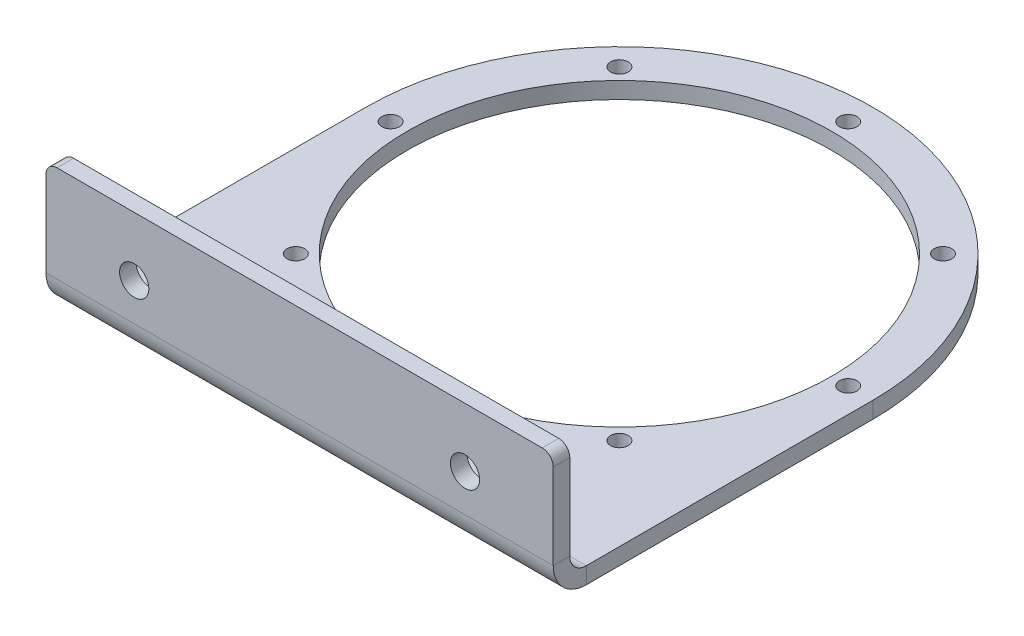
SolidWorks part; units mm, degrees
note: The reader was unsure of these and kept them because the rebuilt part matched: flange length of "Edge-Flange1".
material "3.3549 (EN-AW 5182)"
ref_plane "Front Plane" through (0, 0, 0) normal (0, 0, 1) x (1, 0, 0)
ref_plane "Top Plane" through (0, 0, 0) normal (0, 1, 0) x (1, 0, 0)
ref_plane "Right Plane" through (0, 0, 0) normal (1, 0, 0) x (0, 0, -1)
sketch "Sketch1" plane through (0, 0, 0) normal (0, 1, 0) x (1, 0, 0)
  line L0 (0, -44.7868) -> (0, 44.7868) construction
  line L1 (-46, 0) -> (-46, -55)
  line L2 (-46, -55) -> (46, -55)
  line L3 (46, -55) -> (46, 0)
  line L4 (-44.2539, 0) -> (44.2539, 0) construction
  circle A0 centre (0, 0) radius 38.5
  arc A1 (46, 0) -> (-46, 0) centre (0, 0) ccw
  circle A2 centre (0, 41.5) radius 1
  circle A3 centre (29.3449, 29.3449) radius 1
  circle A4 centre (41.5, 0) radius 1
  circle A5 centre (29.3449, -29.3449) radius 1
  circle A6 centre (0, -41.5) radius 1
  circle A7 centre (-29.3449, -29.3449) radius 1
  circle A8 centre (-41.5, 0) radius 1
  circle A9 centre (-29.3449, 29.3449) radius 1
  point P10 (0, -55)
  point P25 (0, 0)
  dimension "D1" = 92
  dimension "D2" = 77
  dimension "D3" = 2
  dimension "D4" = 41.5
  dimension "D7" = 55
  dimension "D5" = 8
base flange "Base-Flange1" sketch "Sketch1" thickness 3 reverse thickness direction no parameters "D1"=3
edge flange "Edge-Flange1" sketch "Sketch8" flange angle 90 flange length 23.5 flange position material outside bend radius 3 thickness 3 relief rectangular parameters "D1"=2.5, "D6"=10
sketch "Sketch8" plane through (0, 0, 55) normal (0, 0, 1) x (1, 0, 0)
  line L0 (-46, 0) -> (46, 0) construction
  line L1 (-46, 0) -> (46, 0)
  line L2 (-46, 0) -> (-46, 20.5)
  line L3 (-46, 20.5) -> (46, 20.5)
  line L4 (46, 20.5) -> (46, 0)
  line L5 (0, -44.7868) -> (0, 44.7868) construction
  circle A0 centre (-30, 9.8) radius 1
  circle A1 centre (30, 9.8) radius 1
  dimension "D2" = 30
  dimension "D5" = 2
  dimension "D1" = 20.5
  dimension "D3" = 30
  dimension "D4" = 9.8
bend "EdgeBend1" bend radius 3 bend angle 90 parameters "D5"=1
fillet "Fillet1" radius 2 2 edges at (46, 20.5, 56.5) (-46, 20.5, 56.5)
sketch "Sketch12" plane through (0, 0, 0) normal (0, 1, 0) x (1, 0, 0)
  point P0 (-29.3449, 29.3449)
  point P3 (0, 41.5)
  point P6 (-41.5, 0)
  point P9 (-29.3449, -29.3449)
  point P12 (0, -41.5)
  point P15 (29.3449, -29.3449)
  point P18 (41.5, 0)
  point P21 (29.3449, 29.3449)
hole_wizard "M3 Clearance Hole1" positions "Sketch12" profile "Sketch11" hole size "M3" standard "ANSI Metric"
sketch "Sketch11" plane through (-29.3449, 0, -29.3449) normal (1, 0, 0) x (0, 0, 1)
  line L0 (0, 0) -> (0, 136.9614)
  line L1 (0, 136.9614) -> (1.6, 136)
  line L2 (1.6, 136) -> (1.6, 0)
  line L5 (1.6, 0) -> (0, 0)
  line L10 (0, 136.9614) -> (-1.6, 136) construction
  line L11 (0, -6.35) -> (0, 107.95) construction
  dimension "Hole Dia." = 3.2
  dimension "Hole Depth" = 136
  dimension "Drill Angle" = 118
sketch "Sketch16" plane through (0, 0, 58) normal (0, 0, 1) x (1, 0, 0)
  point P0 (-30, 9.8)
  point P3 (30, 9.8)
hole_wizard "M5 Clearance Hole1" positions "Sketch16" profile "Sketch15" hole size "M5" standard "ANSI Metric"
sketch "Sketch15" plane through (-30, 9.8, 58) normal (1, 0, 0) x (0, -1, 0)
  line L0 (0, 0) -> (0, 137.5923)
  line L1 (0, 137.5923) -> (2.65, 136)
  line L2 (2.65, 136) -> (2.65, 0)
  line L5 (2.65, 0) -> (0, 0)
  line L10 (0, 137.5923) -> (-2.65, 136) construction
  line L11 (0, -6.35) -> (0, 107.95) construction
  dimension "Hole Dia." = 5.3
  dimension "Hole Depth" = 136
  dimension "Drill Angle" = 118
sketch "Bend-Lines1" [suppressed] plane through (0, 0, 0) normal (0, 1, 0) x (1, 0, 0)
sketch "Bounding-Box1" [suppressed] plane through (0, 0, 0) normal (0, 1, 0) x (1, 0, 0)
sheet metal parameters "Sheet-Metal8" thickness 3 parameters "D1"=1.6
flat pattern "Flat-Pattern8" [suppressed]
sketch "Bend-Lines2" plane through (0, 0, 0) normal (0, 1, 0) x (1, 0, 0)
sketch3d "Bounding-Box2" [suppressed]
  line L0 (45, 45, 0) -> (45, -50, 0) construction
  line L1 (-45, 45, 0) -> (-45, -50, 0) construction
  line L2 (45, 45, 0) -> (-45, 45, 0) construction
  line L3 (45, -50, 0) -> (-45, -50, 0) construction
sheet metal parameters "Sheet-Metal9" thickness 3 parameters "D1"=1.6
flat pattern "Flat-Pattern8"
sketch "Bend-Lines2" plane through (0, 0, 0) normal (0, 1, 0) x (1, 0, 0)
  line L0 (-45, -50.8347) -> (45, -50.8347) construction
  line L1 (-45, -50.8347) -> (45, -50.8347) construction
sketch3d "Bounding-Box2" [suppressed]
  line L0 (45, 45, 0) -> (45, -63.6695, 0) construction
  line L1 (-45, 45, 0) -> (-45, -63.6695, 0) construction
  line L2 (45, 45, 0) -> (-45, 45, 0) construction
  line L3 (45, -63.6695, 0) -> (-45, -63.6695, 0) construction
bend of the flat pattern "Flatten-<EdgeBend1>1"
sheet metal parameters "Sheet-Metal11" thickness 3 parameters "D1"=1.6
flat pattern "Flat-Pattern8"
sketch "Bend-Lines2" plane through (0, 0, 0) normal (0, 1, 0) x (1, 0, 0)
  line L0 (-46, -55.6416) -> (46, -55.6416) construction
  line L1 (-46, -55.6416) -> (46, -55.6416) construction
sketch3d "Bounding-Box2" [suppressed]
  line L0 (-46, 46, 0) -> (-46, -75.2832, 0) construction
  line L1 (46, 46, 0) -> (46, -75.2832, 0) construction
  line L2 (-46, 46, 0) -> (46, 46, 0) construction
  line L3 (-46, -75.2832, 0) -> (46, -75.2832, 0) construction
bend of the flat pattern "Flatten-<EdgeBend1>1"
sheet metal parameters "Sheet-Metal12" thickness 3 parameters "D1"=1.6
flat pattern "Flat-Pattern8"
sketch "Bend-Lines2" plane through (0, 0, 0) normal (0, 1, 0) x (1, 0, 0)
  line L0 (-46, -55.1) -> (46, -55.1) construction
  line L1 (-46, -55.1) -> (46, -55.1) construction
sketch3d "Bounding-Box2" [suppressed]
  line L0 (-46, 46, 0) -> (-46, -75.7, 0) construction
  line L1 (46, 46, 0) -> (46, -75.7, 0) construction
  line L2 (-46, 46, 0) -> (46, 46, 0) construction
  line L3 (-46, -75.7, 0) -> (46, -75.7, 0) construction
bend of the flat pattern "Flatten-<EdgeBend1>1"
